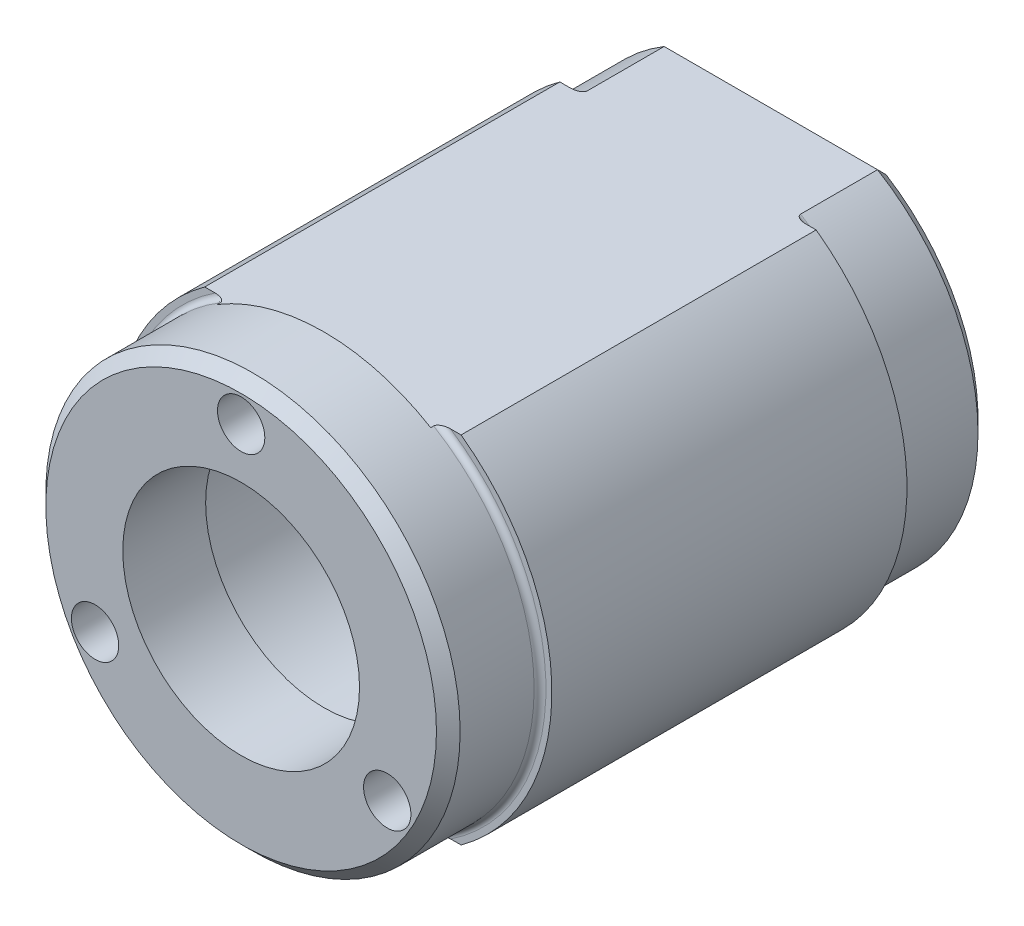
SolidWorks part; units mm, degrees
material "1.0503 (C45)"
ref_plane "Front Plane" through (0, 0, 0) normal (0, 0, 1) x (1, 0, 0)
ref_plane "Top Plane" through (0, 0, 0) normal (0, 1, 0) x (1, 0, 0)
ref_plane "Right Plane" through (0, 0, 0) normal (1, 0, 0) x (0, 0, -1)
sketch "Sketch1" plane through (0, 0, 0) normal (0, 0, 1) x (1, 0, 0)
  line L0 (0, 24.7328) -> (0, -23.7417) construction
  line L1 (-10.8282, 15) -> (10.8282, 15)
  line L2 (-10.8282, -15) -> (10.8282, -15)
  circle A0 centre (0, 0) radius 11.5
  circle A1 centre (0, 0) radius 17.5
  circle A2 centre (0, 0) radius 18.5
  point P6 (0, 15)
  point P7 (0, -15)
  dimension "D1" = 15
  dimension "D2" = 37
  dimension "D3" = 35
  dimension "D5" = 15
  dimension "D4" = 23
extrude "Boss-Extrude1" add sketch "Sketch1" along normal blind 22.75 and the other way blind 23 contours L1 L0 A0 L2 A1 | L0 L1 A1 L2 A0 region at (4.5069, 14.6527, 0) region at (-0.3473, 13.25, 0)
extrude "Boss-Extrude2" add sketch "Sketch1<23>" along normal blind 15 and the other way blind 15 contours L2 A2 L1 A1 | L1 A2 L2 A1 region at (-9.921, 14.6854, 0) region at (16.1906, 8.2807, 0)
sketch "Sketch1<23>" plane through (0, 0, 0) normal (0, 0, 1) x (1, 0, 0) same geometry as "Sketch1"
ref_plane "Plane1" through (0, 0, 22.75) normal (0, 0, 1) x (1, 0, 0)
sketch "Sketch5" plane through (0, 0, 22.75) normal (0, 0, 1) x (1, 0, 0)
  line L0 (0, 24.7328) -> (0, -23.7417) construction
  line L1 (-10.8282, 15) -> (10.8282, 15)
  line L2 (-10.8282, -15) -> (10.8282, -15)
  circle A0 centre (0, 0) radius 10
  circle A1 centre (0, 0) radius 17.5
  circle A2 centre (0, 0) radius 18.5
  point P6 (0, 15)
  point P7 (0, -15)
  dimension "D1" = 15
  dimension "D2" = 37
  dimension "D3" = 35
  dimension "D5" = 15
  dimension "D4" = 20
extrude "Boss-Extrude3" add sketch "Sketch5" against normal blind 7 contours L0 L1 A1 L2 A0 | L1 L0 A0 L2 A1 | L0 A1 L1 | A1 L0 L1 | L2 L0 A1 | L0 L2 A1 region at (3.4149, 16.0064, 22.75) region at (-3.4149, 16.0064, 22.75) region at (4.5069, 14.6527, 22.75) region at (-0.3473, 12.5, 22.75) region at (-3.4149, -16.0064, 22.75) region at (3.4149, -16.0064, 22.75)
sketch "Sketch6" plane through (0, 0, 22.75) normal (0, 0, 1) x (1, 0, 0)
  line L0 (0, 0) -> (0, 22.9778) construction
  circle A0 centre (0, 14.25) radius 2
  circle A1 centre (12.3409, -7.125) radius 2
  circle A2 centre (-12.3409, -7.125) radius 2
  point P3 (0, 14.25)
  point P13 (0, 0)
  dimension "D2" = 4
  dimension "D1" = 14.25
  dimension "D3" = 3
extrude "Cut-Extrude1" cut sketch "Sketch6" against normal blind 5
ref_plane "Plane2" through (0, 0, -20) normal (0, 0, -1) x (-1, 0, 0)
hole_wizard "M3 Tapped Hole1" positions "Sketch8" profile "Sketch9" tap size "M3" standard "ISO"
sketch "Sketch8" plane through (0, -15, 0) normal (0, -1, 0) x (-1, 0, 0)
  point P0 (0, 0)
sketch "Sketch9" plane through (0, -15, 0) normal (1, 0, 0) x (0, 0, -1)
  line L0 (0, 0) -> (0, 8.2511)
  line L1 (0, 8.2511) -> (1.25, 7.5)
  line L2 (1.25, 7.5) -> (1.25, 0.275)
  line L3 (1.25, 0.275) -> (1.525, 0)
  line L5 (1.525, 0) -> (0, 0)
  line L6 (-1.25, 0.275) -> (-1.525, 0) construction
  line L10 (0, 8.2511) -> (-1.25, 7.5) construction
  line L11 (0, -6.35) -> (0, 107.95) construction
  dimension "Tap Drill Dia." = 2.5
  dimension "Tap Drill Depth" = 7.5
  dimension "Near C'Sink Dia." = 3.05
  dimension "Near C'Sink Angle" = 90
  dimension "Drill Angle" = 118
sketch "Sketch7" plane through (0, 0, -20) normal (0, 0, -1) x (-1, 0, 0)
  circle A0 centre (0, 0) radius 16
  circle A1 centre (0, 0) radius 20
  dimension "D1" = 32
fillet "Fillet2" radius 0.5 4 edges at (-17.5, 0, -15) (17.5, 0, -15) (17.5, 0, 15) (-17.5, 0, 15)
chamfer "Chamfer1" distance 1 angle 45 3 edges at (17.5, 0, 22.75) (17.5, 0, -23) (-17.5, 0, -23)
chamfer "Chamfer2" distance 1 angle 45 2 edges at (0, -15, -23) (0, 15, -23)
